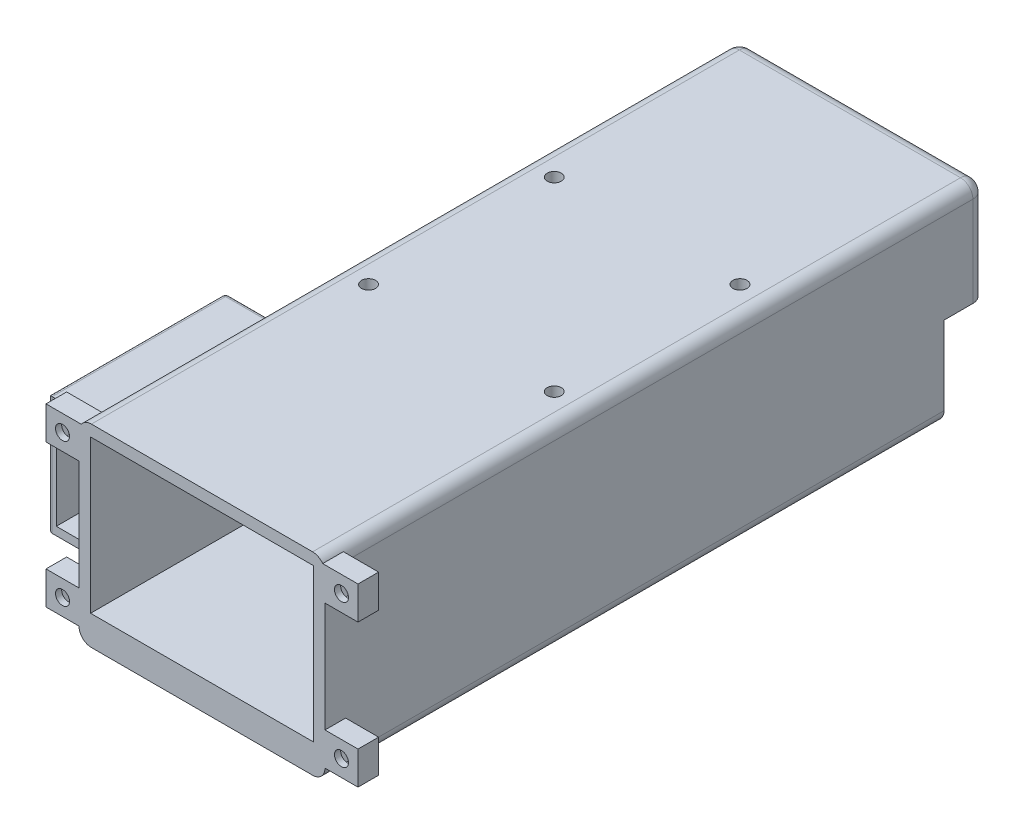
SolidWorks part; units mm, degrees
material "ABS"
ref_plane "Front Plane" through (0, 0, 0) normal (0, 0, 1) x (1, 0, 0)
ref_plane "Top Plane" through (0, 0, 0) normal (0, 1, 0) x (1, 0, 0)
ref_plane "Right Plane" through (0, 0, 0) normal (1, 0, 0) x (0, 0, -1)
sketch "Sketch1" plane through (0, 0, 0) normal (0, 0, 1) x (1, 0, 0)
  line L0 (-27, 18.5) -> (27, -18.5) construction
  line L1 (-27, 18.5) -> (27, 18.5)
  line L2 (-27, 18.5) -> (-27, -18.5)
  line L3 (-27, -18.5) -> (27, -18.5)
  line L4 (27, 18.5) -> (27, -18.5)
  line L5 (-29.8, 21.3) -> (-29.8, -21.3)
  line L6 (-29.8, -21.3) -> (29.8, -21.3)
  line L7 (29.8, 21.3) -> (29.8, -21.3)
  line L8 (-29.8, 21.3) -> (29.8, 21.3)
  point P4 (0, 0)
  dimension "D1" = 54
  dimension "D2" = 37
  dimension "D3" = 2.8
extrude "Boss-Extrude1" add sketch "Sketch1" along normal mid plane 158
sketch "Sketch2" plane through (0, 0, -79) normal (0, 0, -1) x (-1, 0, 0)
  line L1 (-29.8, 21.3) -> (29.8, 21.3)
  line L2 (-29.8, 21.3) -> (-29.8, -21.3)
  line L3 (-29.8, -21.3) -> (29.8, -21.3)
  line L4 (29.8, 21.3) -> (29.8, -21.3)
extrude "Boss-Extrude2" add sketch "Sketch2" along normal blind 2
sketch "Sketch4" plane through (0, 21.3, 0) normal (0, 1, 0) x (1, 0, 0)
  circle A0 centre (-22.5344, 28.8905) radius 1.7
  circle A1 centre (22.4656, 28.8905) radius 1.7
  circle A2 centre (22.4656, -16.1095) radius 1.7
  circle A3 centre (-22.5344, -16.1095) radius 1.7
  dimension "D1" = 3.4
  dimension "D2" = 3.4
  dimension "D3" = 3.4
  dimension "D4" = 3.4
extrude "Cut-Extrude1" cut sketch "Sketch4" against normal blind 71.5
ref_plane "Plane1" through (0, -8.5, 0) normal (0, 1, 0) x (1, 0, 0)
sketch "Sketch5" plane through (0, -8.5, 0) normal (0, 1, 0) x (1, 0, 0)
  circle A0 centre (22.4656, 28.8905) radius 2.75
  circle A1 centre (22.4656, -16.1095) radius 2.75
  circle A2 centre (-22.5344, 28.8905) radius 2.75
  circle A3 centre (-22.5344, -16.1095) radius 2.75
  dimension "D1" = 5.5
extrude "Cut-Extrude2" cut sketch "Sketch5" against normal blind 12.5
sketch "Sketch6" plane through (0, 0, 79) normal (0, 0, 1) x (1, 0, 0)
  line L1 (29.8, -21.3) -> (29.8, -25.5935)
  line L12 (29.8, -21.3) -> (29.8, 21.3) construction
  line L13 (29.8, -21.3) -> (-29.8, -21.3)
  line L14 (-29.8, 21.3) -> (-29.8, -21.3) construction
  line L15 (-29.8, -21.3) -> (-29.8, -25.5935)
  line L16 (29.8, -25.5935) -> (-29.8, -25.5935)
  line L18 (29.8, -21.3) -> (-29.8, -21.3) construction
  dimension "D1" = 4.2935
extrude "Boss-Extrude3" add sketch "Sketch6" against normal up to surface (160 mm away) up to face at (0, 0, -81)
sketch "Sketch7" plane through (0, -21.3, 0) normal (0, 1, 0) x (1, 0, 0)
  circle A0 centre (-22.5344, 28.8905) radius 1.7
  circle A1 centre (22.4656, 28.8905) radius 1.7
  circle A2 centre (22.4656, -16.1095) radius 1.7
  circle A3 centre (-22.5344, -16.1095) radius 1.7
fillet "Fillet1" radius 3 8 edges at (29.8, -2.1468, -81) (-29.8, -2.1468, -81) (0, 21.3, -81) (29.8, 21.3, -1) (-29.8, 21.3, -1) (29.8, -25.5935, -1) (0, -25.5935, -81) (-29.8, -25.5935, -1)
sketch "Sketch8" plane through (0, -25.5935, 0) normal (0, -1, 0) x (1, 0, 0)
  line L1 (31.1274, -71) -> (-33.3525, -71)
  line L25 (-33.3525, -71) -> (-33.3525, -82.8689)
  line L26 (-33.3525, -82.8689) -> (31.1274, -82.8689)
  line L27 (31.1274, -82.8689) -> (31.1274, -71)
  point P6 (0, 0)
sketch "Sketch9" plane through (-29.8, 0, 0) normal (-1, 0, 0) x (0, 0, 1)
  line L0 (79, 18.3) -> (79, -22.5935) construction
  line L1 (29, 11.3) -> (70, 11.3)
  line L2 (29, 11.3) -> (29, -13.4)
  line L3 (29, -13.4) -> (70, -13.4)
  line L6 (27, 13.3) -> (27, -15.4)
  line L7 (27, -15.4) -> (70, -15.4)
  line L9 (27, 13.3) -> (70, 13.3)
  line L10 (70, 13.3) -> (70, 11.3)
  line L11 (27, 13.3) -> (72, 13.3) construction
  line L12 (72, 13.3) -> (72, -15.4) construction
  line L13 (27, -15.4) -> (72, -15.4) construction
  line L14 (70, 11.3) -> (70, -13.4) construction
  line L15 (70, -13.4) -> (70, -15.4)
  dimension "D1" = 41
  dimension "D2" = 24.7
  dimension "D3" = 50
  dimension "D5" = 2
extrude "Boss-Extrude4" add sketch "Sketch9" along normal blind 14.5
sketch "Sketch10" plane through (-44.3, 0, 0) normal (-1, 0, 0) x (0, 0, 1)
  line L1 (27, 13.3) -> (70, 13.3)
  line L2 (27, 13.3) -> (27, -15.4)
  line L3 (27, -15.4) -> (70, -15.4)
  line L4 (70, 13.3) -> (70, -15.4)
extrude "Boss-Extrude5" add sketch "Sketch10" along normal blind 2
sketch "Sketch11" plane through (-46.3, 0, 0) normal (-1, 0, 0) x (0, 0, 1)
  line L0 (70, -1.05) -> (58, -1.05) construction
  line L1 (70, -15.4) -> (70, 13.3) construction
  line L2 (58, 11.3) -> (58, -13.4)
  line L6 (44, -13.4) -> (44, 11.3)
  line L9 (44, 11.3) -> (58, 11.3)
  line L10 (44, -13.4) -> (58, -13.4)
  dimension "D1" = 12
  dimension "D2" = 14
extrude "Cut-Extrude5" cut sketch "Sketch11" against normal blind 2
sketch "Sketch12" plane through (0, 0, 27) normal (0, 0, -1) x (-1, 0, 0)
  line L0 (38.05, 13.3) -> (38.05, -1.05) construction
  line L1 (46.3, 13.3) -> (29.8, 13.3) construction
  line L3 (38.05, -1.05) -> (46.3, -1.05) construction
  line L4 (46.3, 13.3) -> (46.3, -15.4) construction
  line L5 (38.05, -1.05) -> (38.05, -15.4) construction
  line L6 (46.3, -15.4) -> (29.8, -15.4) construction
  line L8 (35.05, 9.125) -> (41.05, 9.125)
  line L9 (35.05, 9.125) -> (35.05, 3.125)
  line L10 (35.05, 3.125) -> (41.05, 3.125)
  line L11 (41.05, 9.125) -> (41.05, 3.125)
  line L12 (35.05, 9.125) -> (41.05, 3.125) construction
  line L13 (35.05, 3.125) -> (41.05, 9.125) construction
  line L14 (35.05, -5.225) -> (41.05, -5.225)
  line L15 (35.05, -5.225) -> (35.05, -11.225)
  line L16 (35.05, -11.225) -> (41.05, -11.225)
  line L17 (41.05, -5.225) -> (41.05, -11.225)
  line L18 (35.05, -5.225) -> (41.05, -11.225) construction
  line L19 (35.05, -11.225) -> (41.05, -5.225) construction
  point P1 (38.05, 6.125)
  point P15 (38.05, -8.225)
  dimension "D1" = 6
  dimension "D2" = 6
  dimension "D3" = 6
  dimension "D4" = 6
extrude "Cut-Extrude6" cut sketch "Sketch12" against normal blind 2
fillet "Fillet2" radius 1 6 edges at (-46.3, -1.05, 70) (-46.3, -15.4, 48.5) (-38.05, -15.4, 27) (-46.3, -1.05, 27) (-46.3, 13.3, 48.5) (-38.05, 13.3, 27)
extrude "Cut-Extrude7" cut sketch "Sketch7" against normal blind 10
extrude "Cut-Extrude8" cut sketch "Sketch8" against normal blind 22
sketch "Sketch13" plane through (0, 0, 79) normal (0, 0, 1) x (1, 0, 0)
  line L5 (0, 21.3) -> (0, -25.5935) construction
  line L8 (26.8, 21.3) -> (-26.8, 21.3) construction
  line L9 (-29.8, 18.3) -> (-29.8, -22.5935) construction
  line L10 (-26.8, -25.5935) -> (26.8, -25.5935) construction
  line L11 (-37.8, -14.5935) -> (-29.8, -14.5935)
  line L13 (27, -18.5) -> (27, 18.5) construction
  line L14 (27, -1.2752) -> (-27, -1.2752) construction
  line L15 (-27, 18.5) -> (-27, -18.5) construction
  line L28 (-37.8, -22.5935) -> (-29.8, -14.5935) construction
  line L29 (29.8, 12.0431) -> (37.8, 20.0431) construction
  line L30 (37.8, -22.5935) -> (29.8, -14.5935) construction
  line L31 (-37.8, 20.0431) -> (-37.8, 12.0431)
  line L32 (-37.8, 20.0431) -> (-29.2417, 20.0431)
  line L33 (-37.8, 12.0431) -> (-29.8, 12.0431)
  line L34 (-29.8, 11.3) -> (-29.8, 13.3) construction
  line L35 (-29.8, 12.0431) -> (-29.8, 18.3)
  line L36 (-29.8, 12.0431) -> (-37.8, 20.0431) construction
  line L37 (-37.8, -14.5935) -> (-37.8, -22.5935)
  line L38 (-37.8, -22.5935) -> (-29.8, -22.5935)
  line L39 (-29.8, -14.5935) -> (-29.8, -22.5935)
  line L40 (29.8, -14.5935) -> (29.8, -22.5935)
  line L41 (37.8, -22.5935) -> (29.8, -22.5935)
  line L42 (37.8, -14.5935) -> (37.8, -22.5935)
  line L43 (29.8, 12.0431) -> (29.8, 18.3)
  line L44 (37.8, 12.0431) -> (29.8, 12.0431)
  line L45 (37.8, 20.0431) -> (29.2417, 20.0431)
  line L46 (37.8, 20.0431) -> (37.8, 12.0431)
  line L47 (37.8, -14.5935) -> (29.8, -14.5935)
  circle A0 centre (-33.8, 16.0431) radius 1.7
  circle A3 centre (-33.8, -18.5935) radius 1.7
  arc A4 (-26.8, 21.3) -> (-29.8, 18.3) centre (-26.8, 18.3) ccw construction
  arc A5 (29.2417, 20.0431) -> (29.8, 18.3) centre (26.8, 18.3) cw
  circle A6 centre (33.8, -18.5935) radius 1.7
  arc A7 (-26.8, 21.3) -> (-29.8, 18.3) centre (-26.8, 18.3) ccw
  arc A8 (-29.2417, 20.0431) -> (-29.8, 18.3) centre (-26.8, 18.3) ccw
  circle A9 centre (33.8, 16.0431) radius 1.7
  point P40 (-33.8, 16.0431)
  point P49 (0, 0)
  dimension "D2" = 3.4
  dimension "D1" = 0
  dimension "D3" = 8
  dimension "D4" = 8
  dimension "D5" = 3
  dimension "D6" = 8
extrude "Boss-Extrude6" add sketch "Sketch13" against normal blind 5
sketch "Sketch14" plane through (0, 0, 74) normal (0, 0, -1) x (-1, 0, 0)
  line L0 (-29.8, 12.0431) -> (-37.8, 20.0431) construction
  line L1 (-30.3359, 16.0431) -> (-32.0679, 19.0431)
  line L2 (-32.0679, 19.0431) -> (-35.5321, 19.0431)
  line L3 (-35.5321, 19.0431) -> (-37.2641, 16.0431)
  line L4 (-37.2641, 16.0431) -> (-35.5321, 13.0431)
  line L5 (-35.5321, 13.0431) -> (-32.0679, 13.0431)
  line L6 (-32.0679, 13.0431) -> (-30.3359, 16.0431)
  line L7 (0, 21.3) -> (0, -1.3573) construction
  line L8 (0, 21.3) -> (0, -25.5935) construction
  line L9 (0, -1.3573) -> (-27, -1.2752) construction
  line L10 (29.8, 12.0431) -> (37.8, 20.0431) construction
  line L11 (32.0679, 13.0431) -> (30.3359, 16.0431)
  line L12 (35.5321, 13.0431) -> (32.0679, 13.0431)
  line L13 (37.2641, 16.0431) -> (35.5321, 13.0431)
  line L14 (35.5321, 19.0431) -> (37.2641, 16.0431)
  line L15 (32.0679, 19.0431) -> (35.5321, 19.0431)
  line L16 (30.3359, 16.0431) -> (32.0679, 19.0431)
  line L17 (29.718, -14.9386) -> (37.6692, -22.9871) construction
  line L18 (-29.8809, -14.5763) -> (-37.9294, -22.5275) construction
  line L19 (30.2295, -18.9418) -> (31.9433, -21.9523)
  line L20 (31.9433, -21.9523) -> (35.4074, -21.9733)
  line L21 (35.4074, -21.9733) -> (37.1576, -18.9839)
  line L22 (37.1576, -18.9839) -> (35.4438, -15.9734)
  line L23 (35.4438, -15.9734) -> (31.9798, -15.9524)
  line L24 (31.9798, -15.9524) -> (30.2295, -18.9418)
  line L25 (-32.1549, -15.5624) -> (-30.4411, -18.5729)
  line L26 (-35.6189, -15.5414) -> (-32.1549, -15.5624)
  line L27 (-37.3692, -18.5308) -> (-35.6189, -15.5414)
  line L28 (-35.6554, -21.5413) -> (-37.3692, -18.5308)
  line L29 (-32.1914, -21.5623) -> (-35.6554, -21.5413)
  line L30 (-30.4411, -18.5729) -> (-32.1914, -21.5623)
  circle A0 centre (-33.8, 16.0431) radius 3 construction
  circle A1 centre (33.8, 16.0431) radius 3 construction
  circle A2 centre (33.6936, -18.9628) radius 3 construction
  circle A3 centre (-33.9052, -18.5519) radius 3 construction
  point P10 (-33.8, 16.0431)
  dimension "D1" = 6
extrude "Cut-Extrude9" cut sketch "Sketch14" against normal blind 3.5
